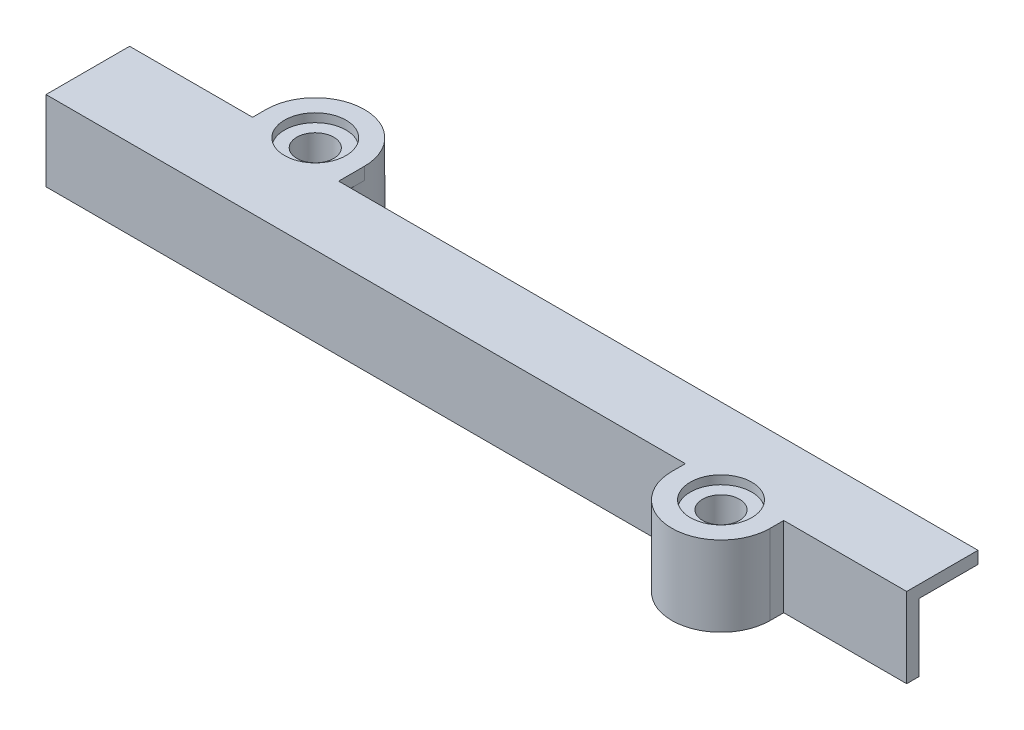
SolidWorks part; units mm, degrees
ref_plane "Front Plane" through (0, 0, 0) normal (0, 0, 1) x (1, 0, 0)
ref_plane "Top Plane" through (0, 0, 0) normal (0, 1, 0) x (1, 0, 0)
ref_plane "Right Plane" through (0, 0, 0) normal (1, 0, 0) x (0, 0, -1)
sketch "Sketch1" plane through (0, 0, 0) normal (0, 1, 0) x (1, 0, 0)
  line L0 (-21, 4.5) -> (21, 4.5) construction
  line L1 (21, 4.5) -> (21, -4.5) construction
  line L2 (21, -4.5) -> (-21, 4.5) construction
  circle A0 centre (-21, 4.5) radius 4
  circle A1 centre (21, -4.5) radius 4
  point P4 (0, 0)
  point P6 (21, -4.5)
  dimension "D1" = 8
  dimension "D2" = 42
  dimension "D3" = 9
extrude "Boss-Extrude1" add sketch "Sketch1" along normal blind 6.5
sketch "Sketch2" plane through (0, 6.5, 0) normal (0, 1, 0) x (1, 0, 0)
  circle A0 centre (-21, 4.5) radius 1.5
  circle A1 centre (21, -4.5) radius 1.5
  dimension "3" = 3
extrude "Cut-Extrude1" cut sketch "Sketch2" against normal blind 6.5
sketch "Sketch3" plane through (0, 6.5, 0) normal (0, 1, 0) x (1, 0, 0)
  circle A0 centre (-21, 4.5) radius 2.5
  circle A1 centre (21, -4.5) radius 2.5
  dimension "D1" = 5
extrude "Cut-Extrude2" cut sketch "Sketch3" against normal blind 0.7
sketch "Sketch4" plane through (0, 6.5, 0) normal (0, 1, 0) x (1, 0, 0)
  line L0 (-17, 4.5) -> (-17, 2.4)
  line L1 (-35, -2.4) -> (35, -2.4)
  line L2 (-35, -2.4) -> (-35, 2.4)
  line L3 (-35, 2.4) -> (35, 2.4)
  line L4 (35, -2.4) -> (35, 2.4)
  line L5 (-35, -2.4) -> (35, 2.4) construction
  line L6 (-35, 2.4) -> (35, -2.4) construction
  line L7 (-25, 4.5) -> (-25, 2.4)
  line L8 (17, -4.5) -> (17, -2.4)
  line L9 (25, -4.5) -> (25, -2.4)
  circle A0 centre (-21, 4.5) radius 4 construction
  circle A1 centre (-21, 4.5) radius 4
  circle A2 centre (21, -4.5) radius 4 construction
  circle A3 centre (21, -4.5) radius 4
  point P0 (0, 0)
  circle M7 centre (-21, 4.5) radius 4
  dimension "D1" = 4.8
  dimension "D2" = 10
extrude "Boss-Extrude2" add sketch "Sketch4" against normal blind 1 contours A3 L1 L4 L3 L2 M7 | L7 L3 M7 | L3 L0 M7 | A3 L1 L8 | A3 L9 L1 region at (-17.1761, 6.5, -2.9169) region at (0, 6.5, 0) region at (-24.8239, 6.5, -2.9169) region at (24.8239, 6.5, 2.9169) region at (17.1761, 6.5, 2.9169)
sketch "Sketch5" plane through (0, 6.5, 0) normal (0, 1, 0) x (1, 0, 0)
  line L0 (25, -4.5) -> (25, -2.4) construction
  line L1 (35, -2.4) -> (25, -2.4)
  line L2 (35, -2.4) -> (35, -3.4)
  line L3 (35, -3.4) -> (25, -3.4)
  line L4 (25, -2.4) -> (25, -3.4)
  line L5 (17, -4.5) -> (17, -2.4) construction
  line L6 (-35, -2.4) -> (17, -2.4)
  line L7 (-35, -2.4) -> (-35, -3.4)
  line L8 (-35, -3.4) -> (17, -3.4)
  line L9 (17, -2.4) -> (17, -3.4)
  line L10 (-25, 4.5) -> (-25, 2.4) construction
  line L11 (-35, 2.4) -> (-25, 2.4)
  line L12 (-35, 2.4) -> (-35, 3.4)
  line L13 (-35, 3.4) -> (-25, 3.4)
  line L14 (-25, 2.4) -> (-25, 3.4)
  dimension "D1" = 1
  dimension "D2" = 1
  dimension "D3" = 1
extrude "Boss-Extrude3" add sketch "Sketch5" against normal up to surface (6.5 mm away) up to face at (21, 0, 6)
sketch "Sketch6" plane through (0, 0, 0) normal (0, -1, 0) x (1, 0, 0)
  line L2 (-25, -2.4) -> (-25, -3.4)
  line L5 (-25, -4.5) -> (-24, -4.5)
  line L6 (-25, -4.5) -> (-25, -2.4)
  line L7 (-25, -2.4) -> (-24, -2.4)
  line L8 (-24, -4.5) -> (-24, -2.4)
  line L9 (17, 2.4) -> (18, 2.4)
  line L10 (17, 2.4) -> (17, 4.5)
  line L11 (17, 4.5) -> (18, 4.5)
  line L12 (18, 2.4) -> (18, 4.5)
  line L13 (25, 2.4) -> (24, 2.4)
  line L14 (25, 2.4) -> (25, 4.5)
  line L15 (25, 4.5) -> (24, 4.5)
  line L16 (24, 2.4) -> (24, 4.5)
  circle A0 centre (21, 4.5) radius 4 construction
  point P16 (17, 4.5)
  point P20 (25, 4.5)
  circle M15 centre (21, 4.5) radius 4
  dimension "D1" = 1
  dimension "D2" = 1
  dimension "D3" = 1
extrude "Boss-Extrude4" add sketch "Sketch6" against normal up to surface (5.5 mm away) contours L13 L14 M15 | L10 L9 M15 | L5 L8 L7 L2 L6 region at (-24.5, 0, -3.45) region at (17.1761, 0, 2.9169) region at (24.8239, 0, 2.9169) up to face at (1.1333, 5.5, 0.2267)
sketch "Sketch7" plane through (0, 0, 0) normal (0, -1, 0) x (1, 0, 0)
  line L1 (-21, -1.5266) -> (-23.575, -3.0133)
  line L2 (-23.575, -3.0133) -> (-23.575, -5.9867)
  line L3 (-23.575, -5.9867) -> (-21, -7.4734)
  line L4 (-21, -7.4734) -> (-18.425, -5.9867)
  line L5 (-18.425, -5.9867) -> (-18.425, -3.0133)
  line L6 (-18.425, -3.0133) -> (-21, -1.5266)
  line L7 (21, 7.4734) -> (18.425, 5.9867)
  line L8 (18.425, 5.9867) -> (18.425, 3.0133)
  line L9 (18.425, 3.0133) -> (21, 1.5266)
  line L10 (21, 1.5266) -> (23.575, 3.0133)
  line L11 (23.575, 3.0133) -> (23.575, 5.9867)
  line L12 (23.575, 5.9867) -> (21, 7.4734)
  circle A0 centre (-21, -4.5) radius 2.575 construction
  circle A1 centre (21, 4.5) radius 2.575 construction
  dimension "D1" = 5.15
  dimension "D2" = 5.15
extrude "Cut-Extrude3" cut sketch "Sketch7" against normal blind 1
